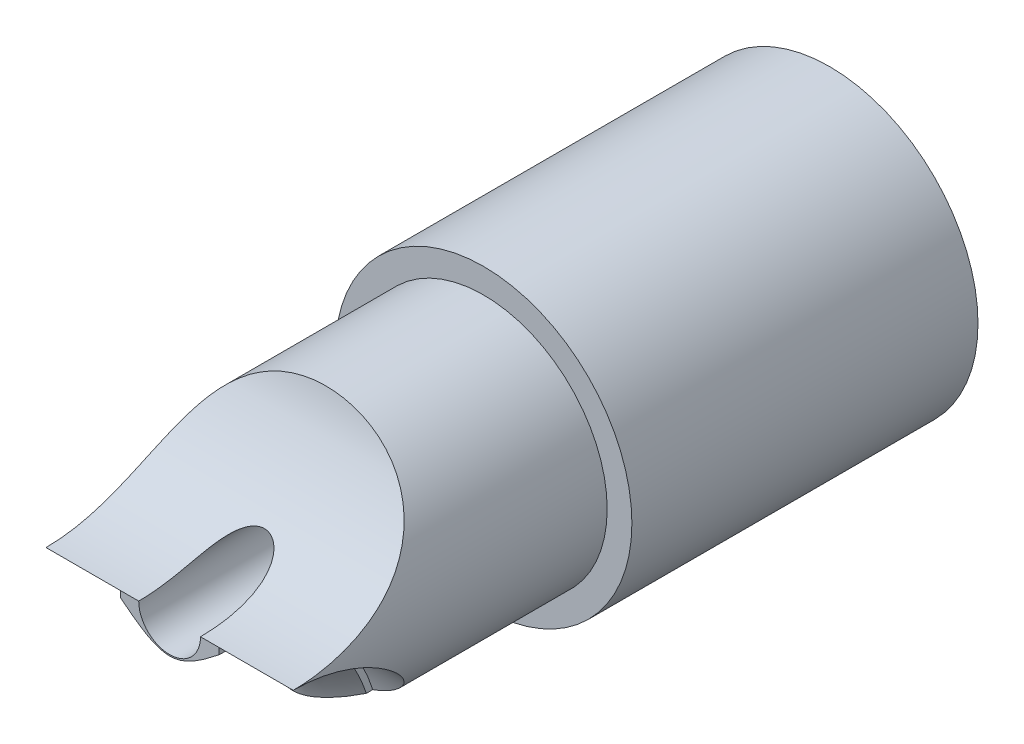
SolidWorks part; units mm, degrees
ref_plane "Front" through (0, 0, 0) normal (0, 0, 1) x (1, 0, 0)
ref_plane "Top" through (0, 0, 0) normal (0, 1, 0) x (1, 0, 0)
ref_plane "Right" through (0, 0, 0) normal (1, 0, 0) x (0, 0, -1)
sketch "Base sketch" plane through (0, 0, 0) normal (0, 0, 1) x (1, 0, 0)
  circle A0 centre (0, 0) radius 6
  dimension "D1" = 12
extrude "Boss-Extrude1" add sketch "Base sketch" along normal blind 14
sketch "Sketch2" plane through (0, 0, 14) normal (0, 0, 1) x (1, 0, 0)
  circle A0 centre (0, 0) radius 5
  dimension "D1" = 10
extrude "Boss-Extrude2" add sketch "Sketch2" along normal blind 12.7
sketch "Sketch3" plane through (0, 0, 26.7) normal (0, 0, 1) x (1, 0, 0)
  circle A0 centre (0, 0) radius 1.25
  dimension "D1" = 2.5
extrude "Cut-Extrude1" cut sketch "Sketch3" against normal through all
sketch "Sketch4" plane through (0, 0, 0) normal (0, 0, -1) x (-1, 0, 0)
  circle A0 centre (0, 0) radius 2.25
  dimension "D1" = 4.5
extrude "Cut-Extrude2" cut sketch "Sketch4" against normal blind 5
sketch "Sketch5" plane through (0, 0, 0) normal (1, 0, 0) x (0, 0, -1)
  line L0 (-26.7, 6.5) -> (-26.7, -6.5) construction
  line L4 (-26.7, 1.25) -> (-26.7, -1.25) construction
  circle A0 centre (-26.7, 6.5) radius 6.5
  circle A1 centre (-26.7, -6.5) radius 6.5
  point P2 (-26.7, 0)
  dimension "D1" = 13
extrude "Cut-Extrude3" cut sketch "Sketch5" against normal through all and the other way through all contours A0 region at (0, 6.5, 26.7)
ref_plane "Plane1" through (0.0071, 0, 0) normal (1, 0, 0) x (0, 0, -1)
ref_plane "Plane2" through (2.0071, 0, 0) normal (1, 0, 0) x (0, 0, -1)
ref_plane "Plane3" through (-1.9929, 0, 0) normal (1, 0, 0) x (0, 0, -1)
sketch "Sketch6" plane through (0.0071, 0, 0) normal (1, 0, 0) x (0, 0, -1)
  circle A0 centre (-26.7, -6.5) radius 5.2
  circle A1 centre (-26.7, -6.5) radius 6.5
  circle A2 centre (-26.7, -6.5) radius 6.5
  dimension "D1" = 0
sketch "Sketch7" plane through (2.0071, 0, 0) normal (1, 0, 0) x (0, 0, -1)
  circle A1 centre (-26.7, -6.5) radius 6.25
  circle A2 centre (-26.7, -6.5) radius 6.5
sketch "Sketch8" plane through (-1.9929, 0, 0) normal (1, 0, 0) x (0, 0, -1)
  circle A1 centre (-26.7, -6.5) radius 6.25
  circle A2 centre (-26.7, -6.5) radius 6.5
loft "Loft1" add section "Sketch8" section "Sketch6" section "Sketch7" connector at (-1.9929, -12.75, 26.7) connector at (0.0071, -11.7, 26.7) connector at (2.0071, -12.75, 26.7)
combine bodies "Combine3" operation type subtract main body 105 bodies to subtract 106
extrude "Cut-Extrude5" cut sketch "Sketch8<4>" against normal blind 10 contours A2
sketch "Sketch8<4>" plane through (-1.9929, 0, 0) normal (1, 0, 0) x (0, 0, -1) same geometry as "Sketch8"
extrude "Cut-Extrude6" cut sketch "Sketch7<5>" along normal blind 10 contours A2
sketch "Sketch7<5>" plane through (2.0071, 0, 0) normal (1, 0, 0) x (0, 0, -1) same geometry as "Sketch7"
